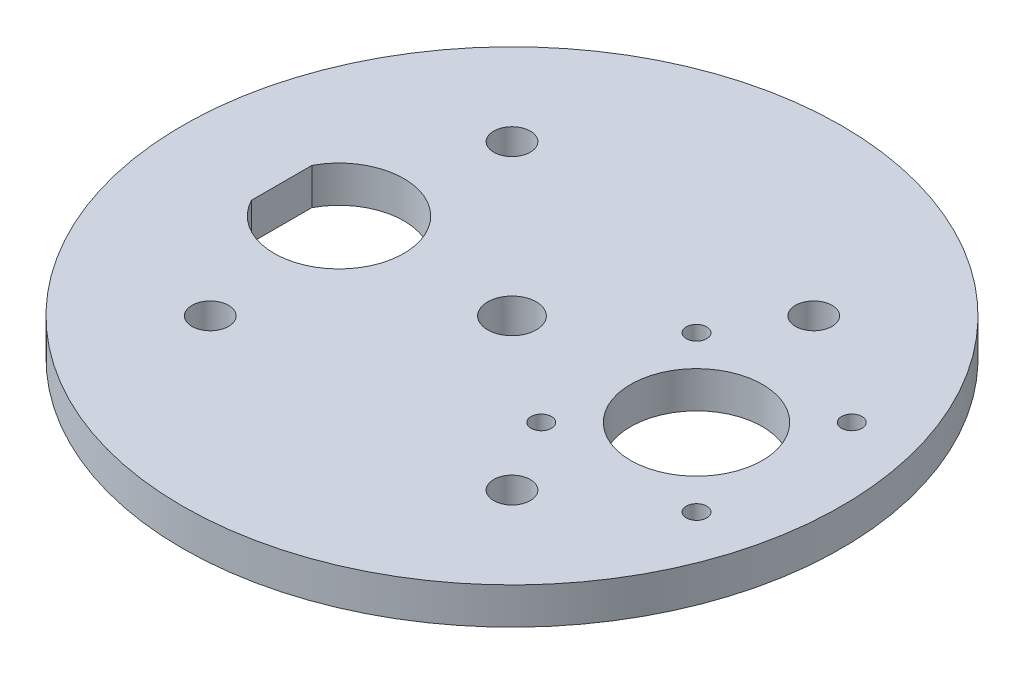
SolidWorks part; units mm, degrees
ref_plane "Front Plane" through (0, 0, 0) normal (0, 0, 1) x (1, 0, 0)
ref_plane "Top Plane" through (0, 0, 0) normal (0, 1, 0) x (1, 0, 0)
ref_plane "Right Plane" through (0, 0, 0) normal (1, 0, 0) x (0, 0, -1)
sketch "Sketch2" plane through (0, 0, 0) normal (0, 1, 0) x (1, 0, 0)
  circle A0 centre (0, 0) radius 57.15
  dimension "D1" = 114.3
extrude "Boss-Extrude1" add sketch "Sketch2" along normal blind 6.35 contours A0
sketch "Sketch6" plane through (0, 6.35, 0) normal (0, 1, 0) x (1, 0, 0)
  circle A0 centre (-26.1629, -26.1629) radius 3.175
  circle A1 centre (26.1629, -26.1629) radius 3.175
  circle A2 centre (-26.1629, 26.1631) radius 3.175
  circle A3 centre (26.1629, 26.1631) radius 3.175
  dimension "D1" = 6.35
  dimension "D2" = 74
  dimension "D3" = 26.1629
  dimension "D4" = 26.1629
  dimension "D5" = 26.1629
extrude "Cut-Extrude1" cut sketch "Sketch6" against normal up to next
sketch "Sketch7" plane through (0, 6.35, 0) normal (0, 1, 0) x (1, 0, 0)
  circle A0 centre (32, 0) radius 11.43
  circle A3 centre (18.54, -13.464) radius 1.778
  circle A4 centre (18.54, 13.46) radius 1.778
  circle A5 centre (45.46, 13.46) radius 1.778
  circle A6 centre (45.46, -13.464) radius 1.778
  dimension "D1" = 22.86
  dimension "D2" = 3.556
  dimension "D3" = 3.556
  dimension "D4" = 3.556
  dimension "D5" = 3.556
  dimension "D6" = 13.46
  dimension "D7" = 13.46
  dimension "D8" = 13.46
  dimension "D9" = 13.464
  dimension "D10" = 32
extrude "Cut-Extrude2" cut sketch "Sketch7" against normal through all
sketch "Sketch8" plane through (0, 6.35, 0) normal (0, 1, 0) x (1, 0, 0)
  line L0 (-39.95, 5.2498) -> (-39.95, -5.2498)
  circle A2 centre (0, 0) radius 4.2164
  arc A3 (-39.95, -5.2498) -> (-39.95, 5.2498) centre (-30, 0) ccw
  dimension "D1" = 9.95
  dimension "D3" = 8.4328
  dimension "D4" = 22.5
  dimension "D5" = 30
extrude "Cut-Extrude3" cut sketch "Sketch8" against normal through all
equation "\"width\"=26.1629"
equation "\"D4@Sketch6\"=\"width\""
equation "\"D3@Sketch6\"=\"width\""
equation "\"D5@Sketch6\"=\"width\""
